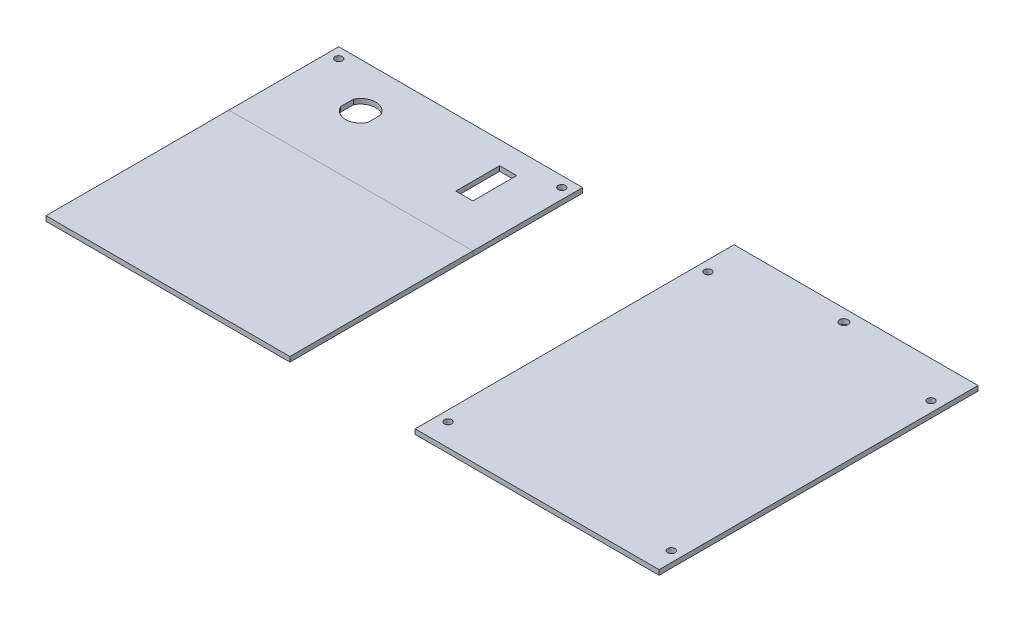
SolidWorks part; units mm, degrees
ref_plane "Front Plane" through (0, 0, 0) normal (0, 0, 1) x (1, 0, 0)
ref_plane "Top Plane" through (0, 0, 0) normal (0, 1, 0) x (1, 0, 0)
ref_plane "Right Plane" through (0, 0, 0) normal (1, 0, 0) x (0, 0, -1)
sketch "Sketch1" plane through (0, 0, 0) normal (0, 1, 0) x (1, 0, 0)
  line L0 (4.25, 40.75) -> (95.75, 40.75) construction
  line L1 (0, 0) -> (100, 0)
  line L2 (0, 0) -> (0, 45)
  line L3 (0, 45) -> (100, 45)
  line L4 (100, 0) -> (100, 45)
  line L5 (21.6434, 29.352) -> (21.6434, 24.148)
  line L6 (0, 0) -> (100, 0)
  line L7 (0, 0) -> (0, -75)
  line L8 (0, -75) -> (100, -75)
  line L9 (100, 0) -> (100, -75)
  line L10 (75.25, 35.75) -> (82.25, 35.75)
  line L11 (75.25, 35.75) -> (75.25, 17.75)
  line L12 (75.25, 17.75) -> (82.25, 17.75)
  line L13 (82.25, 35.75) -> (82.25, 17.75)
  line L14 (75.25, 35.75) -> (82.25, 17.75) construction
  line L15 (75.25, 17.75) -> (82.25, 35.75) construction
  line L16 (155.6043, 40.75) -> (247.1043, 40.75) construction
  line L17 (32.8434, 29.352) -> (32.8434, 24.148)
  line L18 (151.3543, -75) -> (251.3543, -75)
  line L19 (151.3543, -75) -> (151.3543, 55.75)
  line L20 (151.3543, 55.75) -> (251.3543, 55.75)
  line L21 (251.3543, -75) -> (251.3543, 55.75)
  circle A0 centre (4.25, 40.75) radius 1.5
  circle A1 centre (95.75, 40.75) radius 1.5
  arc A2 (21.6434, 24.148) -> (32.8434, 24.148) centre (27.2434, 26.75) ccw
  arc A3 (32.8434, 29.352) -> (21.6434, 29.352) centre (27.2434, 26.75) ccw
  circle A4 centre (155.6043, 40.75) radius 1.5
  circle A5 centre (247.1043, 40.75) radius 1.5
  circle A6 centre (247.1043, -65.75) radius 1.5
  circle A7 centre (155.6043, -65.75) radius 1.5
  circle A8 centre (201.3543, 50.75) radius 1.75
  point P9 (50, 40.75)
  point P10 (50, 0)
  point P13 (78.75, 26.75)
  point P35 (201.3543, 40.75)
  point P36 (201.3543, 55.75)
  point P37 (0, 0)
  dimension "D4" = 3
  dimension "D11" = 12.35
  dimension "D13" = 3
  dimension "D17" = 3.5
  dimension "D1" = 100
  dimension "D2" = 45
  dimension "D3" = 91.5
  dimension "D5" = 120
  dimension "D6" = 8.5
  dimension "D7" = 17
  dimension "D8" = 7
  dimension "D9" = 18
  dimension "D10" = 5
  dimension "D12" = 11.2
  dimension "D14" = 91.5
  dimension "D15" = 106.5
  dimension "D16" = 15
  dimension "D18" = 5
extrude "Boss-Extrude1" add sketch "Sketch1" along normal blind 2 contours L18 L21 L20 L19 A8 A7 A6 A5 A4 | L1 L4 L3 L2 A3 L17 A2 L5 A1 A0 L10 L13 L12 L11 region at (49.7672, 0, -22.1971) region at (201.3543, 0, 9.6633)
extrude "Boss-Extrude2" add sketch "Sketch1<3>" along normal blind 2 separate body contours L9 L1 L7 L8 region at (50, 0, 37.5)
sketch "Sketch1<3>" plane through (0, 0, 0) normal (0, 1, 0) x (1, 0, 0) same geometry as "Sketch1"
